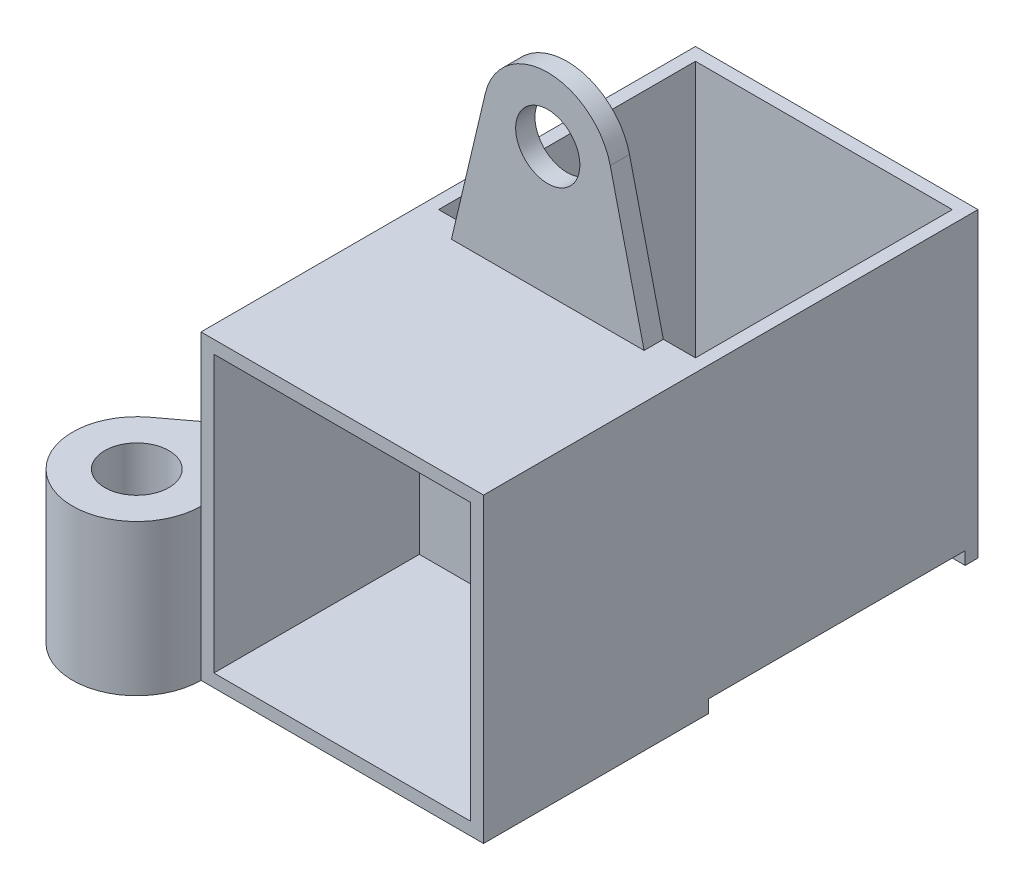
SolidWorks part; units mm, degrees
note: The reader was unsure of these and kept them because the rebuilt part matched: shared geometry of "Sketch1<3>", "Sketch1<4>", "Sketch1<7>", "Sketch1<8>", "Sketch6<4>".
ref_plane "Front Plane" through (0, 0, 0) normal (0, 0, 1) x (1, 0, 0)
ref_plane "Top Plane" through (0, 0, 0) normal (0, 1, 0) x (1, 0, 0)
ref_plane "Right Plane" through (0, 0, 0) normal (1, 0, 0) x (0, 0, -1)
sketch "Sketch1" plane through (0, 0, 0) normal (0, 0, 1) x (1, 0, 0)
  line L0 (-10, 0) -> (10, 0) construction
  line L1 (0, 0) -> (0, -20) construction
  line L2 (-15, -20) -> (15, -20)
  line L3 (9.7321, 2.2991) -> (15, -20)
  line L4 (-9.7321, 2.2991) -> (-15, -20)
  line L6 (-20, -65) -> (20, -65)
  line L7 (-20, -65) -> (-20, -20)
  line L8 (-20, -20) -> (20, -20)
  line L9 (20, -65) -> (20, -20)
  line L10 (-20, -65) -> (20, -20) construction
  line L11 (-20, -20) -> (20, -65) construction
  line L12 (-20, -20) -> (-22, -20)
  line L13 (-20, -20) -> (-20, -65)
  line L14 (-20, -65) -> (-22, -65)
  line L15 (-22, -20) -> (-22, -65)
  line L16 (20, -20) -> (22, -20)
  line L17 (20, -20) -> (20, -65)
  line L18 (20, -65) -> (22, -65)
  line L19 (22, -20) -> (22, -65)
  line L20 (-22, -65) -> (22, -65)
  line L21 (-22, -65) -> (-22, -67)
  line L22 (-22, -67) -> (22, -67)
  line L23 (22, -65) -> (22, -67)
  line L24 (-22, -20) -> (22, -20)
  line L25 (-22, -20) -> (-22, -22)
  line L26 (-22, -22) -> (22, -22)
  line L27 (22, -20) -> (22, -22)
  circle A0 centre (0, 0) radius 5
  circle A1 centre (0, 0) radius 10
  point P7 (0, 0)
  point P11 (0, -20)
  point P13 (0, -42.5)
  point P18 (0, -65)
  dimension "D1" = 10
  dimension "D2" = 20
  dimension "D3" = 20
  dimension "D4" = 30
  dimension "D5" = 40
  dimension "D6" = 45
  dimension "D7" = 2
  dimension "D8" = 2
  dimension "D9" = 2
  dimension "D10" = 2
extrude "Boss-Extrude1" add sketch "Sketch1" against normal blind 3 contours A1 A0 | A1 L4 L2 L3 | L6 L9 L8 L2 L7 | L13 L26 L17 L8 L2
extrude "Boss-Extrude2" add sketch "Sketch1<3>" against normal blind 40 and the other way blind 35 from surface at -3 contours L12 L15 L14 L7 | L19 L16 L9 L18 | L15 L26 L13 L12 | L17 L26 L19 L16 starting at face at (5, 0, -3)
sketch "Sketch1<3>" plane through (0, 0, 0) normal (0, 0, 1) x (1, 0, 0) same geometry as "Sketch1"
extrude "Boss-Extrude6" add sketch "Sketch1<4>" along normal up to surface (35 mm away) from surface at -3 contours L23 L18 L6 L14 L21 L22 starting at face at (5, 0, -3)
sketch "Sketch1<4>" plane through (0, 0, 0) normal (0, 0, 1) x (1, 0, 0) same geometry as "Sketch1"
extrude "Boss-Extrude8" add sketch "Sketch1<7>" against normal blind 2 from surface contours L6 L9 L8 L2 L7 | L19 L16 L9 L18 | L12 L15 L14 L7 | L23 L18 L6 L14 L21 L22 | L13 L26 L17 L8 L2 | L15 L26 L13 L12 | L17 L26 L19 L16
sketch "Sketch1<7>" plane through (0, 0, 0) normal (0, 0, 1) x (1, 0, 0) same geometry as "Sketch1"
extrude "Boss-Extrude9" add sketch "Sketch1<8>" along normal up to surface (35 mm away) from surface at -3 contours L13 L26 L17 L8 L2 | L17 L26 L19 L16 | L15 L26 L13 L12 up to face at (0, -43, 32) starting at face at (5, 0, -3)
sketch "Sketch1<8>" plane through (0, 0, 0) normal (0, 0, 1) x (1, 0, 0) same geometry as "Sketch1"
sketch "Sketch6" plane through (0, 0, 0) normal (0, 1, 0) x (1, 0, 0)
  line L0 (22, -32) -> (-22, -32) construction
  line L1 (-22, -32) -> (-22, 45) construction
  line L2 (-32, -32) -> (-3.8782, -32) construction
  line L3 (-38, -24) -> (-22, -12)
  line L4 (-22, -12) -> (-22, -32)
  circle A0 centre (-32, -32) radius 5
  circle A1 centre (-32, -32) radius 10
  dimension "D1" = 20
  dimension "D2" = 10
  dimension "D3" = 20
extrude "Boss-Extrude10" add sketch "Sketch6" along normal blind 23.5 from surface at -67 separate body
extrude "Cut-Extrude1" cut sketch "Sketch6<4>" against normal through all from surface at -43.5 starting at face at (-29.4907, -43.5, 26.9814)
sketch "Sketch6<4>" plane through (0, 0, 0) normal (0, 1, 0) x (1, 0, 0) same geometry as "Sketch6"
